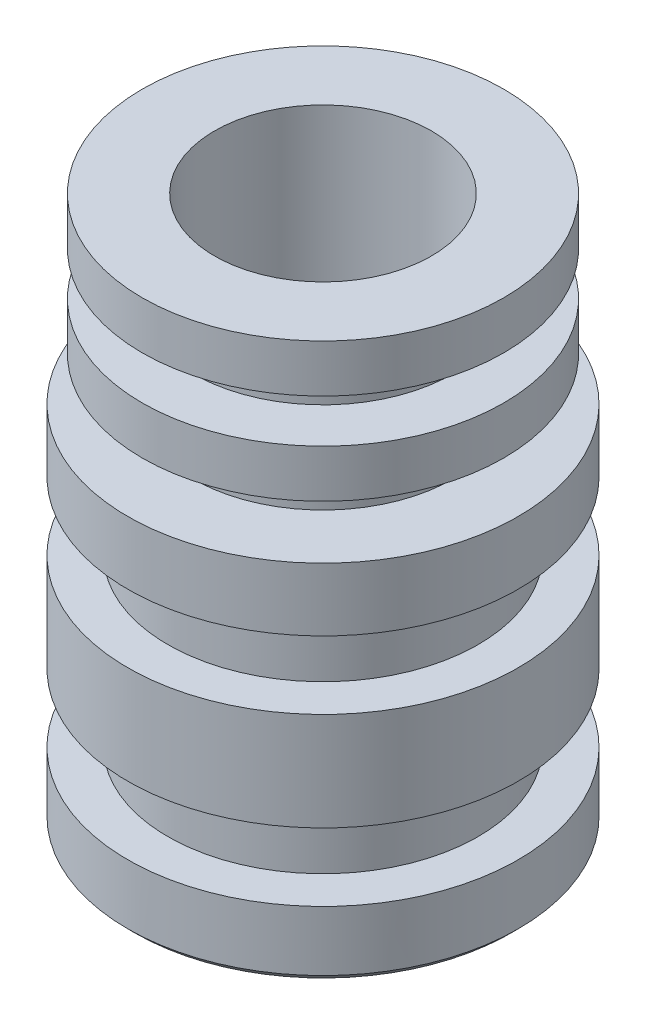
SolidWorks part; units mm, degrees
material "AISI 316 Barre d'acier inoxydable recuit (SS)"
ref_plane "Plan de face" through (0, 0, 0) normal (0, 0, 1) x (1, 0, 0)
ref_plane "Plan de dessus" through (0, 0, 0) normal (0, 1, 0) x (1, 0, 0)
ref_plane "Plan de droite" through (0, 0, 0) normal (1, 0, 0) x (0, 0, -1)
sketch "Esquisse1" plane through (0, 0, 0) normal (0, 0, 1) x (1, 0, 0)
  line L0 (0, -29.1154) -> (0, 30.7029) construction
  line L4 (-2, 15.34) -> (-2, -5.66) construction
  line L5 (-2, -5.66) -> (0, -5.66) construction
  line L9 (0, 0) -> (-13.5, 0)
  line L10 (-13.5, 0) -> (-13.5, 25.2) construction
  line L11 (-2, 15.34) -> (-7.5, 20.84) construction
  line L13 (-12.5, 29.0574) -> (-12.5, 31.5) construction
  line L18 (-12.5, 31.5) -> (-12.5, 28.2)
  line L19 (-12.5, 28.2) -> (-9, 28.2)
  line L20 (-9, 28.2) -> (-9, 25.2)
  line L29 (-9, 25.2) -> (-12.5, 25.2)
  line L33 (-13.5, 25.2) -> (-12.5, 25.2)
  line L35 (-13.5, 25.2) -> (-13.5, 20.84)
  line L36 (-13.5, 16.14) -> (-13.5, 9.34)
  line L37 (-13.5, 4.64) -> (-13.5, 0)
  line L39 (-2, 15.34) -> (-2, -5.66) construction
  line L42 (-7.5, 20.84) -> (-7.5, 8)
  line L43 (-7.5, 8) -> (0, 8)
  line L44 (-13.5, 20.84) -> (-10.73, 20.84)
  line L45 (-10.73, 20.84) -> (-10.73, 16.14)
  line L46 (-10.73, 16.14) -> (-13.5, 16.14)
  line L47 (-13.5, 9.34) -> (-10.73, 9.34)
  line L48 (-10.73, 9.34) -> (-10.73, 4.64)
  line L49 (-10.73, 4.64) -> (-13.5, 4.64)
  line L50 (0, 8) -> (0, 0)
  line L51 (-12.5, 31.5) -> (-9, 31.5)
  line L52 (-9, 31.5) -> (-9, 34.5)
  line L53 (-9, 34.5) -> (-12.5, 34.5)
  line L54 (-12.5, 34.5) -> (-12.5, 37.8)
  line L55 (-12.5, 37.8) -> (-7.5, 37.8)
  line L56 (-7.5, 37.8) -> (-7.5, 20.84)
  point P3 (-13, 25.2)
  point P32 (0, 0)
  point P33 (-8, 31.5)
  point P34 (0, 0)
  dimension "D5" = 4.7
  dimension "D12" = 25.2
  dimension "D7" = 10.73
  dimension "D1" = 2
  dimension "D2" = 13.5
  dimension "D3" = 7.5
  dimension "D4" = 1
  dimension "D6" = 6.8
  dimension "D8" = 4.36
  dimension "D9" = 4.64
  dimension "D10" = 3
  dimension "45" = 45
  dimension "D11" = 8
  dimension "D13" = 21
  dimension "D15" = 3.5
  dimension "D17" = 3.3
revolve "Révolution1" add sketch "Esquisse1" angle 360 about L0
sketch "Esquisse4" plane through (0, 0, 0) normal (0, -1, 0) x (1, 0, 0)
  circle A0 centre (0, 0) radius 2
  dimension "D1" = 4
extrude "Enlèv. mat.-Extru.3" cut sketch "Esquisse4" against normal through all
chamfer "Chanfrein4" distance 0.5 angle 45 2 edges at (0, 8, -2) (0, 0, -2)
chamfer "Chanfrein3" distance 0.5 angle 45 1 edges at (0, 0, -13.5)
equation "\"1à.00mm\"=12"
